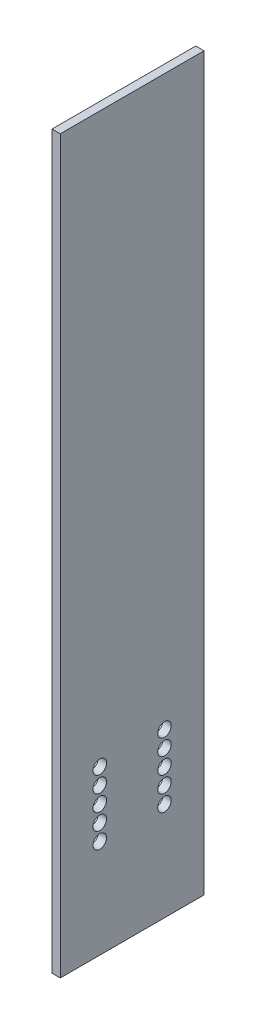
SolidWorks part; units mm, degrees
ref_plane "Front Plane" through (0, 0, 0) normal (0, 0, 1) x (1, 0, 0)
ref_plane "Top Plane" through (0, 0, 0) normal (0, 1, 0) x (1, 0, 0)
ref_plane "Right Plane" through (0, 0, 0) normal (1, 0, 0) x (0, 0, -1)
sketch "Sketch1" plane through (0, 0, 0) normal (1, 0, 0) x (0, 0, -1)
  line L1 (-28.2194, 143.51) -> (28.2194, 143.51)
  line L2 (-28.2194, 143.51) -> (-28.2194, -143.51)
  line L3 (-28.2194, -143.51) -> (28.2194, -143.51)
  line L4 (28.2194, 143.51) -> (28.2194, -143.51)
  line L5 (-28.2194, 143.51) -> (28.2194, -143.51) construction
  line L6 (-28.2194, -143.51) -> (28.2194, 143.51) construction
  point P0 (0, 0)
  dimension "D1" = 56.4388
  dimension "D2" = 287.02
extrude "Boss-Extrude1" add sketch "Sketch1" along normal blind 3.2512
sketch "Sketch2" plane through (0, 0, 0) normal (-1, 0, 0) x (0, 0, 1)
  line L0 (0, 143.51) -> (0, -143.51) construction
  line L1 (-28.2194, 143.51) -> (28.2194, 143.51) construction
  line L2 (28.2194, -143.51) -> (-28.2194, -143.51) construction
  point P7 (-12.7, -98.5012)
  point P9 (12.7, -98.5012)
  dimension "D1" = 12.7
  dimension "D2" = 45.0088
hole_wizard "#4 (0.209) Diameter Hole1" positions "Sketch3" profile "Sketch4" hole size "#4" standard "ANSI Inch" end condition through all
sketch "Sketch3" plane through (0, 0, 0) normal (-1, 0, 0) x (0, 0, 1)
  point P0 (-12.7, -98.5012)
  point P3 (12.7, -98.5012)
sketch "Sketch4" plane through (0, -98.5012, -12.7) normal (0, 1, 0) x (0, 0, 1)
  line L0 (0, 0) -> (0, 3.2512)
  line L1 (0, 3.2512) -> (2.6543, 3.2512)
  line L2 (2.6543, 3.2512) -> (2.6543, 0)
  line L5 (2.6543, 0) -> (0, 0)
  line L11 (0, -6.35) -> (0, 107.95) construction
  dimension "Thru Hole Dia." = 5.3086
  dimension "Thru Hole Depth" = 3.2512
pattern_linear "LPattern1" count 4 spacing 6.35 along (0, 1, 0) count 2 spacing 6.35 along (0, -1, 0) of "#4 (0.209) Diameter Hole1" pattern seed only yes
equation "\"motor offset\"=6mm"
equation "\"thickness0.25\"=0.225in"
equation "\"thickness0.125\"=0.122in"
equation "\"thickness_acrylic0.1\"= 0.1in"
equation "\"D1@Sketch1\"=\"thickness_acrylic0.1\"+\"thickness0.125\"+2"
equation "\"D2@Sketch2\"=\"thickness0.125\"+0.5+1.15"
